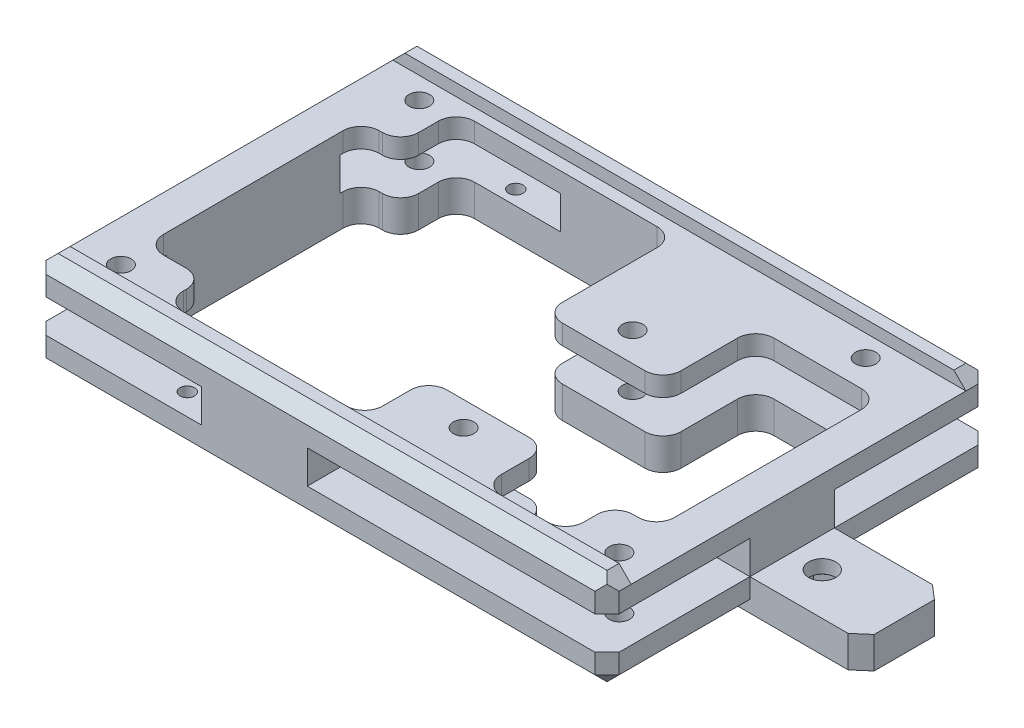
SolidWorks part; units mm, degrees
ref_plane "Front Plane" through (0, 0, 0) normal (0, 0, 1) x (1, 0, 0)
ref_plane "Top Plane" through (0, 0, 0) normal (0, 1, 0) x (1, 0, 0)
ref_plane "Right Plane" through (0, 0, 0) normal (1, 0, 0) x (0, 0, -1)
sketch "Sketch2" plane through (0, 0, 0) normal (0, 1, 0) x (1, 0, 0)
  line L1 (47.5, 31.75) -> (-47.5, 31.75)
  line L2 (47.5, 31.75) -> (47.5, -31.75)
  line L3 (47.5, -31.75) -> (-47.5, -31.75)
  line L4 (-47.5, 31.75) -> (-47.5, -31.75)
  line L5 (47.5, 31.75) -> (-47.5, -31.75) construction
  line L6 (47.5, -31.75) -> (-47.5, 31.75) construction
  point P0 (0, 0)
  dimension "D1" = 95
  dimension "D2" = 63.5
extrude "Boss-Extrude1" add sketch "Sketch2" along normal blind 16
hole_wizard "M3 Clearance Hole1" positions "Sketch7" profile "Sketch8" hole size "M3" standard "ANSI Metric" end condition through all
sketch "Sketch7" plane through (0, 16, 0) normal (0, 1, 0) x (1, 0, 0)
  line L1 (-40.6667, 24.17) -> (34.4633, 24.17)
  line L2 (-40.6667, 24.17) -> (-40.6667, -24.17)
  line L3 (-40.6667, -24.17) -> (34.4633, -24.17)
  line L4 (34.4633, 24.17) -> (34.4633, -24.17)
  line L5 (34.4633, -24.17) -> (41.9633, -24.17) construction
  line L12 (41.9633, -24.17) -> (47.5, -24.17) construction
  line L13 (47.5, -31.75) -> (47.5, 31.75) construction
  line L15 (0, 31.75) -> (0, 24.17) construction
  line L16 (47.5, 31.75) -> (-47.5, 31.75) construction
  line L17 (-3.1017, -24.17) -> (-3.1017, -31.75) construction
  line L18 (-47.5, -31.75) -> (47.5, -31.75) construction
  line L19 (11.1433, -19.17) -> (11.1433, -24.17) construction
  point P33 (-40.6667, -24.17)
  point P34 (34.4633, 24.17)
  point P43 (41.9633, -24.17)
  point P74 (11.1433, -19.17)
  point P80 (11.1433, 8.85)
  point P85 (-3.1017, -24.17)
  point P88 (-39.5367, 24.17)
  dimension "D1" = 48.34
  dimension "D2" = 75.13
  dimension "D3" = 7.5
  dimension "D4" = 51.81
  dimension "D5" = 5
  dimension "D6" = 28.02
  dimension "D7" = 1.13
sketch "Sketch8" plane through (-39.5367, 16, -24.17) normal (1, 0, 0) x (0, 0, 1)
  line L0 (0, 0) -> (0, 16)
  line L1 (0, 16) -> (1.7, 16)
  line L2 (1.7, 16) -> (1.7, 0.025)
  line L3 (1.7, 0.025) -> (1.725, 0)
  line L5 (1.725, 0) -> (0, 0)
  line L6 (-1.7, 0.025) -> (-1.725, 0) construction
  line L11 (0, -6.35) -> (0, 107.95) construction
  dimension "Thru Hole Dia." = 3.4
  dimension "Thru Hole Depth" = 16
  dimension "Near C'Sink Dia." = 3.45
  dimension "Near C'Sink Angle" = 90
sketch "Sketch9" plane through (0, 16, 0) normal (0, 1, 0) x (1, 0, 0)
  line L0 (-34.9742, 19.4874) -> (-34.9742, 22.75)
  line L2 (-37.9742, 16.4874) -> (-38.5, 16.4874)
  line L3 (-41.5, 13.4874) -> (-41.5, -16.2525)
  line L4 (-38.5, -19.2525) -> (-34.7301, -19.2525)
  line L5 (-31.7301, -22.2525) -> (-31.7301, -22.75)
  line L6 (-31.9742, 25.75) -> (-1.6848, 25.75)
  line L7 (-28.7301, -25.75) -> (-1.6848, -25.75)
  line L8 (1.3152, -22.75) -> (1.3152, -18.118)
  line L9 (4.3152, -15.118) -> (17.9713, -15.118)
  line L10 (20.9713, -18.118) -> (20.9713, -22.75)
  line L11 (23.9713, -25.75) -> (31.6479, -25.75)
  line L12 (34.6479, -22.75) -> (34.6479, -20.5605)
  line L13 (37.6479, -17.5605) -> (38.5, -17.5605)
  line L14 (41.5, -14.5605) -> (41.5, 16.4283)
  line L15 (38.5, 19.4283) -> (23.9713, 19.4283)
  line L16 (20.9713, 16.4283) -> (20.9713, 7.055)
  line L17 (17.9713, 4.055) -> (4.3152, 4.055)
  line L18 (1.3152, 7.055) -> (1.3152, 22.75)
  line L19 (-47.5, 31.75) -> (-47.5, -31.75) construction
  line L20 (47.5, 31.75) -> (-47.5, 31.75) construction
  line L21 (47.5, -31.75) -> (47.5, 31.75) construction
  line L22 (-47.5, -31.75) -> (47.5, -31.75) construction
  circle A0 centre (41.9633, -24.17) radius 1.725 construction
  circle A1 centre (34.4633, 24.17) radius 1.725 construction
  circle A2 centre (11.1433, 8.85) radius 1.725 construction
  circle A3 centre (11.1433, -19.17) radius 1.725 construction
  circle A4 centre (-40.6667, -24.17) radius 1.725 construction
  circle A6 centre (41.9633, -24.17) radius 1.725 construction
  circle A7 centre (34.4633, 24.17) radius 1.725 construction
  circle A8 centre (11.1433, 8.85) radius 1.725 construction
  circle A9 centre (11.1433, -19.17) radius 1.725 construction
  circle A10 centre (-40.6667, -24.17) radius 1.725 construction
  arc A12 (-34.9742, 22.75) -> (-31.9742, 25.75) centre (-31.9742, 22.75) cw
  arc A13 (-1.6848, 25.75) -> (1.3152, 22.75) centre (-1.6848, 22.75) cw
  arc A14 (4.3152, 4.055) -> (1.3152, 7.055) centre (4.3152, 7.055) cw
  arc A15 (20.9713, 7.055) -> (17.9713, 4.055) centre (17.9713, 7.055) cw
  arc A16 (23.9713, 19.4283) -> (20.9713, 16.4283) centre (23.9713, 16.4283) ccw
  arc A17 (41.5, 16.4283) -> (38.5, 19.4283) centre (38.5, 16.4283) ccw
  arc A18 (38.5, -17.5605) -> (41.5, -14.5605) centre (38.5, -14.5605) ccw
  arc A19 (34.6479, -20.5605) -> (37.6479, -17.5605) centre (37.6479, -20.5605) cw
  arc A20 (31.6479, -25.75) -> (34.6479, -22.75) centre (31.6479, -22.75) ccw
  arc A21 (20.9713, -22.75) -> (23.9713, -25.75) centre (23.9713, -22.75) ccw
  arc A22 (17.9713, -15.118) -> (20.9713, -18.118) centre (17.9713, -18.118) cw
  arc A23 (1.3152, -18.118) -> (4.3152, -15.118) centre (4.3152, -18.118) cw
  arc A24 (-1.6848, -25.75) -> (1.3152, -22.75) centre (-1.6848, -22.75) ccw
  arc A25 (-31.7301, -22.75) -> (-28.7301, -25.75) centre (-28.7301, -22.75) ccw
  arc A26 (-34.7301, -19.2525) -> (-31.7301, -22.2525) centre (-34.7301, -22.2525) cw
  arc A27 (-41.5, -16.2525) -> (-38.5, -19.2525) centre (-38.5, -16.2525) ccw
  arc A28 (-38.5, 16.4874) -> (-41.5, 13.4874) centre (-38.5, 13.4874) ccw
  arc A29 (-34.9742, 19.4874) -> (-37.9742, 16.4874) centre (-37.9742, 19.4874) cw
  point P37 (11.1433, -15.118)
  point P39 (11.1433, 4.055)
  dimension "D5" = 3
  dimension "D1" = 6
  dimension "D2" = 6
  dimension "D3" = 6
  dimension "D4" = 6
extrude "Cut-Extrude1" cut sketch "Sketch9" against normal up to surface (16 mm away) up to face at (-40.6667, 0, 25.87)
sketch "Sketch10" plane through (0, 0, 0) normal (0, -1, 0) x (1, 0, 0)
  line L1 (-40.6667, 20.9946) -> (-37.9167, 22.5823)
  line L2 (-37.9167, 22.5823) -> (-37.9167, 25.7577)
  line L3 (-37.9167, 25.7577) -> (-40.6667, 27.3454)
  line L4 (-40.6667, 27.3454) -> (-43.4167, 25.7577)
  line L5 (-43.4167, 25.7577) -> (-43.4167, 22.5823)
  line L6 (-43.4167, 22.5823) -> (-40.6667, 20.9946)
  line L7 (-39.5367, -27.3454) -> (-36.7867, -25.7577)
  line L8 (-36.7867, -25.7577) -> (-36.7867, -22.5823)
  line L9 (-36.7867, -22.5823) -> (-39.5367, -20.9946)
  line L10 (-39.5367, -20.9946) -> (-42.2867, -22.5823)
  line L11 (-42.2867, -22.5823) -> (-42.2867, -25.7577)
  line L12 (-42.2867, -25.7577) -> (-39.5367, -27.3454)
  line L13 (8.3933, -10.4377) -> (11.1433, -12.0254)
  line L14 (11.1433, -12.0254) -> (13.8933, -10.4377)
  line L15 (13.8933, -10.4377) -> (13.8933, -7.2623)
  line L16 (13.8933, -7.2623) -> (11.1433, -5.6746)
  line L17 (11.1433, -5.6746) -> (8.3933, -7.2623)
  line L18 (8.3933, -7.2623) -> (8.3933, -10.4377)
  line L19 (8.3933, 17.5823) -> (11.1433, 15.9946)
  line L20 (11.1433, 15.9946) -> (13.8933, 17.5823)
  line L21 (13.8933, 17.5823) -> (13.8933, 20.7577)
  line L22 (13.8933, 20.7577) -> (11.1433, 22.3454)
  line L23 (11.1433, 22.3454) -> (8.3933, 20.7577)
  line L24 (8.3933, 20.7577) -> (8.3933, 17.5823)
  line L31 (41.9633, 20.9946) -> (44.7133, 22.5823)
  line L32 (44.7133, 22.5823) -> (44.7133, 25.7577)
  line L33 (44.7133, 25.7577) -> (41.9633, 27.3454)
  line L34 (41.9633, 27.3454) -> (39.2133, 25.7577)
  line L35 (39.2133, 25.7577) -> (39.2133, 22.5823)
  line L36 (39.2133, 22.5823) -> (41.9633, 20.9946)
  circle A1 centre (41.9633, 24.17) radius 1.7 construction
  circle A2 centre (11.1433, 19.17) radius 1.7 construction
  circle A3 centre (11.1433, -8.85) radius 1.7 construction
  circle A5 centre (-40.6667, 24.17) radius 1.7 construction
  circle A7 centre (41.9633, 24.17) radius 1.7 construction
  circle A8 centre (11.1433, 19.17) radius 1.7 construction
  circle A9 centre (11.1433, -8.85) radius 1.7 construction
  circle A11 centre (-40.6667, 24.17) radius 1.7 construction
  circle A12 centre (-40.6667, 24.17) radius 2.75 construction
  circle A13 centre (-39.5367, -24.17) radius 2.75 construction
  circle A14 centre (11.1433, -8.85) radius 2.75 construction
  circle A15 centre (11.1433, 19.17) radius 2.75 construction
  circle A17 centre (41.9633, 24.17) radius 2.75 construction
  circle A18 centre (-39.5367, -24.17) radius 1.7 construction
  circle A19 centre (-39.5367, -24.17) radius 1.7 construction
  dimension "D1" = 5.5
extrude "Cut-Extrude2" cut sketch "Sketch10" against normal blind 2.4
fillet "Fillet2" radius 2 4 edges at (0, 16, -31.75) (47.5, 16, 0) (0, 16, 31.75) (-47.5, 16, 0) profile chamfer
ref_plane "Plane1" through (0, 8, 0) normal (0, 1, 0) x (1, 0, 0)
sketch "Sketch12" plane through (0, 8, 0) normal (0, 1, 0) x (1, 0, 0)
  line L0 (-31.7301, -22.2525) -> (-31.7301, -22.75) construction
  line L1 (-38.5, -19.2525) -> (-34.7301, -19.2525) construction
  line L2 (-31.7301, -22.2525) -> (-31.7301, -22.75)
  line L3 (-38.5, -19.2525) -> (-34.7301, -19.2525)
  line L14 (-40.6667, -24.17) -> (-40.6213, -18.3738) construction
  line L15 (47.5, -31.75) -> (-47.5, -31.75) construction
  line L16 (-47.5, -31.75) -> (-47.5, 31.75) construction
  line L17 (-19.7301, -31.75) -> (-47.5, -31.75)
  line L18 (-47.5, -31.75) -> (-47.5, -15.7525)
  line L23 (-19.7301, -31.75) -> (-19.7301, -25.75)
  line L24 (-28.7301, -25.75) -> (-1.6848, -25.75) construction
  line L25 (-19.7301, -25.75) -> (-28.7301, -25.75)
  line L26 (-47.5, -15.7525) -> (-41.5, -15.7525)
  line L27 (-41.5, 13.4874) -> (-41.5, -16.2525) construction
  line L28 (-41.5, -15.7525) -> (-41.5, -16.2525)
  arc A0 (-31.7301, -22.75) -> (-28.7301, -25.75) centre (-28.7301, -22.75) ccw construction
  arc A1 (-31.7301, -22.2525) -> (-34.7301, -19.2525) centre (-34.7301, -22.2525) ccw construction
  arc A2 (-41.5, -16.2525) -> (-38.5, -19.2525) centre (-38.5, -16.2525) ccw construction
  arc A3 (-31.7301, -22.75) -> (-28.7301, -25.75) centre (-28.7301, -22.75) ccw
  arc A4 (-31.7301, -22.2525) -> (-34.7301, -19.2525) centre (-34.7301, -22.2525) ccw
  arc A5 (-41.5, -16.2525) -> (-38.5, -19.2525) centre (-38.5, -16.2525) ccw
  circle A6 centre (-40.6667, -24.17) radius 1.7 construction
  circle A7 centre (-40.6667, -24.17) radius 1.7
  dimension "D1" = 9
  dimension "D2" = 0.5
extrude "Cut-Extrude3" cut sketch "Sketch12" along normal blind 2.75 and the other way blind 2.75
sketch "Sketch14" plane through (0, 8, 0) normal (0, 1, 0) x (1, 0, 0)
  line L0 (-34.9742, 22.75) -> (-34.9742, 19.4874) construction
  line L1 (-34.9742, 22.75) -> (-34.9742, 19.4874)
  line L3 (-47.5, -31.75) -> (-47.5, 31.75) construction
  line L4 (-47.5, 12.9874) -> (-47.5, 31.75)
  line L5 (-31.9742, 25.75) -> (-31.9742, 31.75) construction
  line L6 (-47.5, 31.75) -> (47.5, 31.75) construction
  line L8 (-47.5, 31.75) -> (-11.9742, 31.75)
  line L9 (-37.9742, 16.4874) -> (-38.5, 16.4874) construction
  line L10 (-37.9742, 16.4874) -> (-38.5, 16.4874)
  line L11 (-31.9742, 25.75) -> (-11.9742, 25.75)
  line L12 (-1.6848, 25.75) -> (-31.9742, 25.75) construction
  line L13 (-11.9742, 25.75) -> (-11.9742, 31.75)
  line L16 (-47.5, 12.9874) -> (-41.5, 12.9874)
  line L17 (-41.5, 13.4874) -> (-41.5, -16.2525) construction
  line L18 (-41.5, 12.9874) -> (-41.5, 13.4874)
  arc A1 (-38.5, 16.4874) -> (-41.5, 13.4874) centre (-38.5, 13.4874) ccw construction
  arc A2 (-37.9742, 16.4874) -> (-34.9742, 19.4874) centre (-37.9742, 19.4874) ccw construction
  arc A3 (-31.9742, 25.75) -> (-34.9742, 22.75) centre (-31.9742, 22.75) ccw construction
  arc A5 (-38.5, 16.4874) -> (-41.5, 13.4874) centre (-38.5, 13.4874) ccw
  arc A6 (-37.9742, 16.4874) -> (-34.9742, 19.4874) centre (-37.9742, 19.4874) ccw
  arc A7 (-31.9742, 25.75) -> (-34.9742, 22.75) centre (-31.9742, 22.75) ccw
  dimension "D1" = 20
  dimension "D2" = 0.5
extrude "Cut-Extrude10" cut sketch "Sketch14" against normal blind 2.75 and the other way blind 2.75
sketch "Sketch13" plane through (0, 8, 0) normal (0, 1, 0) x (1, 0, 0)
  line L1 (20.9713, -18.118) -> (20.9713, -22.75) construction
  line L2 (4.3152, -15.118) -> (17.9713, -15.118) construction
  line L3 (1.3152, -22.75) -> (1.3152, -18.118) construction
  line L4 (47.5, 31.75) -> (47.5, -31.75) construction
  line L5 (20.9713, -18.118) -> (20.9713, -22.75)
  line L6 (4.3152, -15.118) -> (17.9713, -15.118)
  line L7 (1.3152, -22.75) -> (1.3152, -18.118)
  line L9 (37.6479, -17.5605) -> (38.5, -17.5605) construction
  line L10 (34.6479, -22.75) -> (34.6479, -20.5605) construction
  line L12 (23.9713, -25.75) -> (31.6479, -25.75) construction
  line L13 (-2.1848, -31.75) -> (47.5, -31.75)
  line L14 (47.5, -31.75) -> (-47.5, -31.75) construction
  line L15 (47.5, -8.0605) -> (47.5, -31.75)
  line L16 (37.6479, -17.5605) -> (38.5, -17.5605)
  line L18 (34.6479, -22.75) -> (34.6479, -20.5605)
  line L20 (23.9713, -25.75) -> (31.6479, -25.75)
  line L22 (41.5, -14.5605) -> (41.5, -8.0605)
  line L23 (41.5, -14.5605) -> (41.5, 16.4283) construction
  line L24 (41.5, -8.0605) -> (47.5, -8.0605)
  line L25 (-2.1848, -31.75) -> (-2.1848, -25.75)
  line L26 (-28.7301, -25.75) -> (-1.6848, -25.75) construction
  line L27 (-2.1848, -25.75) -> (-1.6848, -25.75)
  arc A0 (-1.6848, -25.75) -> (1.3152, -22.75) centre (-1.6848, -22.75) ccw construction
  arc A1 (20.9713, -22.75) -> (23.9713, -25.75) centre (23.9713, -22.75) ccw construction
  arc A2 (20.9713, -18.118) -> (17.9713, -15.118) centre (17.9713, -18.118) ccw construction
  arc A3 (4.3152, -15.118) -> (1.3152, -18.118) centre (4.3152, -18.118) ccw construction
  arc A4 (-1.6848, -25.75) -> (1.3152, -22.75) centre (-1.6848, -22.75) ccw
  arc A5 (20.9713, -22.75) -> (23.9713, -25.75) centre (23.9713, -22.75) ccw
  arc A6 (20.9713, -18.118) -> (17.9713, -15.118) centre (17.9713, -18.118) ccw
  arc A7 (4.3152, -15.118) -> (1.3152, -18.118) centre (4.3152, -18.118) ccw
  arc A15 (38.5, -17.5605) -> (41.5, -14.5605) centre (38.5, -14.5605) ccw construction
  arc A16 (37.6479, -17.5605) -> (34.6479, -20.5605) centre (37.6479, -20.5605) ccw construction
  arc A17 (31.6479, -25.75) -> (34.6479, -22.75) centre (31.6479, -22.75) ccw construction
  arc A18 (38.5, -17.5605) -> (41.5, -14.5605) centre (38.5, -14.5605) ccw
  arc A19 (37.6479, -17.5605) -> (34.6479, -20.5605) centre (37.6479, -20.5605) ccw
  arc A20 (31.6479, -25.75) -> (34.6479, -22.75) centre (31.6479, -22.75) ccw
  dimension "D1" = 6.5
  dimension "D2" = 0.5
extrude "Cut-Extrude11" cut sketch "Sketch13" against normal blind 2.75 and the other way blind 2.75
sketch "Sketch15" plane through (0, 8, 0) normal (0, 1, 0) x (1, 0, 0)
  line L0 (38.5, 19.4283) -> (23.9713, 19.4283) construction
  line L1 (20.9713, 16.4283) -> (20.9713, 7.055) construction
  line L2 (17.9713, 4.055) -> (4.3152, 4.055) construction
  line L3 (1.3152, 7.055) -> (1.3152, 22.75) construction
  line L4 (38.5, 19.4283) -> (23.9713, 19.4283)
  line L5 (20.9713, 16.4283) -> (20.9713, 7.055)
  line L6 (17.9713, 4.055) -> (4.3152, 4.055)
  line L7 (1.3152, 7.055) -> (1.3152, 22.75)
  line L8 (-1.6848, 25.75) -> (-12.6848, 25.75)
  line L10 (-1.6848, 25.75) -> (-31.9742, 25.75) construction
  line L11 (-12.6848, 25.75) -> (-12.6848, 31.75)
  line L12 (-47.5, 31.75) -> (47.5, 31.75) construction
  line L13 (-12.6848, 31.75) -> (47.5, 31.75)
  line L14 (47.5, 31.75) -> (47.5, 5.9283)
  line L15 (47.5, 31.75) -> (47.5, -31.75) construction
  line L16 (47.5, 5.9283) -> (41.5, 5.9283)
  line L17 (41.5, -14.5605) -> (41.5, 16.4283) construction
  line L18 (41.5, 5.9283) -> (41.5, 16.4283)
  line L19 (11.1433, 8.85) -> (11.1433, 4.055) construction
  line L20 (31.2357, 19.4283) -> (31.2357, 24.17) construction
  line L21 (31.2357, 24.17) -> (34.4633, 24.17) construction
  line L22 (-39.5367, 24.17) -> (-39.5367, 8.85) construction
  line L23 (-39.5367, 8.85) -> (11.1433, 8.85) construction
  circle A0 centre (34.4633, 24.17) radius 1.725 construction
  circle A1 centre (11.1433, 8.85) radius 1.725 construction
  arc A2 (41.5, 16.4283) -> (38.5, 19.4283) centre (38.5, 16.4283) ccw construction
  arc A3 (23.9713, 19.4283) -> (20.9713, 16.4283) centre (23.9713, 16.4283) ccw construction
  arc A4 (17.9713, 4.055) -> (20.9713, 7.055) centre (17.9713, 7.055) ccw construction
  arc A5 (1.3152, 7.055) -> (4.3152, 4.055) centre (4.3152, 7.055) ccw construction
  arc A6 (1.3152, 22.75) -> (-1.6848, 25.75) centre (-1.6848, 22.75) ccw construction
  circle A7 centre (34.4633, 24.17) radius 1.725 construction
  circle A8 centre (11.1433, 8.85) radius 1.725 construction
  arc A9 (41.5, 16.4283) -> (38.5, 19.4283) centre (38.5, 16.4283) ccw
  arc A10 (23.9713, 19.4283) -> (20.9713, 16.4283) centre (23.9713, 16.4283) ccw
  arc A11 (17.9713, 4.055) -> (20.9713, 7.055) centre (17.9713, 7.055) ccw
  arc A12 (1.3152, 7.055) -> (4.3152, 4.055) centre (4.3152, 7.055) ccw
  arc A13 (1.3152, 22.75) -> (-1.6848, 25.75) centre (-1.6848, 22.75) ccw
  circle A16 centre (-40.6667, -24.17) radius 1.7 construction
  circle A17 centre (-40.6667, -24.17) radius 1.7
  circle A18 centre (-39.5367, 24.17) radius 1.725 construction
  circle A19 centre (-39.5367, 24.17) radius 1.725 construction
  dimension "D1" = 11
  dimension "D2" = 10.5
extrude "Cut-Extrude12" cut sketch "Sketch15" against normal blind 2.75 and the other way blind 2.75
chamfer "Chamfer1" distance 2 angle 45 8 edges at (47.5, 0, 0) (47.5, 2.625, -31.75) (47.5, 2.625, 31.75) (0, 0, 31.75) (-47.5, 2.625, 31.75) (-47.5, 0, 0) (0, 0, -31.75) (-47.5, 2.625, -31.75)
chamfer "Chamfer2" distance 2 angle 45 4 edges at (-47.5, 12.375, 31.75) (47.5, 12.375, 31.75) (47.5, 12.375, -31.75) (-47.5, 12.375, -31.75)
sketch "Sketch18" plane through (0, 0, -31.75) normal (0, 0, -1) x (-1, 0, 0)
  line L4 (17.7301, 10.75) -> (0.1848, 10.75)
  line L5 (-45.5, 10.75) -> (45.5, 10.75) construction
  line L6 (0.1848, 10.75) -> (0.1848, 5.25)
  line L7 (-45.5, 5.25) -> (45.5, 5.25) construction
  line L8 (0.1848, 5.25) -> (17.7301, 5.25)
  line L9 (17.7301, 5.25) -> (17.7301, 10.75)
  line L10 (0.1848, 8) -> (2.1848, 8) construction
  line L11 (2.1848, 10.75) -> (2.1848, 5.25) construction
  line L12 (17.7301, 8) -> (19.7301, 8) construction
  line L13 (19.7301, 5.25) -> (19.7301, 10.75) construction
  dimension "D1" = 2
extrude "Boss-Extrude2" add sketch "Sketch18" against normal up to surface (6 mm away) up to face at (-16.8295, 2.625, -25.75)
ref_plane "Plane2" through (0, 0, 1.0661) normal (0, 0, 1) x (1, 0, 0)
sketch "Sketch40" plane through (0, 16, 0) normal (0, 1, 0) x (1, 0, 0)
  line L0 (-62.155, 27.75) -> (62.155, 27.75)
  line L1 (-62.155, -27.75) -> (62.155, -27.75)
  line L2 (62.155, -27.75) -> (62.155, 27.75)
  line L3 (-62.155, 27.75) -> (-62.155, -27.75)
  line L4 (0, -27.75) -> (0, -29.75) construction
  line L5 (-45.5, -29.75) -> (45.5, -29.75) construction
  line L6 (0, 27.75) -> (0, 29.75) construction
  line L7 (45.5, 29.75) -> (-45.5, 29.75) construction
  dimension "D1" = 2
extrude "Cut-Extrude16" cut sketch "Sketch40" against normal blind 2
sketch "Sketch43" plane through (0, 0, 8.0605) normal (0, 0, 1) x (1, 0, 0)
  line L0 (45.5, 2) -> (45.5, 0) construction
  line L1 (45.5, 2) -> (45.5, 0)
  line L2 (45.5, 0) -> (57.5, 0)
  line L3 (57.5, 0) -> (60.0844, 5.25)
  line L4 (60.0844, 5.25) -> (47.5, 5.25)
  line L5 (47.5, 5.25) -> (47.5, 2)
  line L6 (47.5, 2) -> (45.5, 2)
  dimension "D1" = 10
extrude "Boss-Extrude3" add sketch "Sketch43" against normal up to surface (13.9888 mm away) up to face at (44.5, 8, -5.9283)
sketch "Sketch48" plane through (0, 0, 0) normal (0, -1, 0) x (1, 0, 0)
  line L0 (47.5, 8.0605) -> (47.5, -5.9283) construction
  line L2 (47.5, 8.0605) -> (57.5, 8.0605) construction
  line L3 (52.5, -2.8887) -> (55.925, -0.9113)
  line L4 (55.925, -0.9113) -> (55.925, 3.0435)
  line L5 (55.925, 3.0435) -> (52.5, 5.021)
  line L6 (52.5, 5.021) -> (49.075, 3.0435)
  line L7 (49.075, 3.0435) -> (49.075, -0.9113)
  line L8 (49.075, -0.9113) -> (52.5, -2.8887)
  circle A0 centre (52.5, 1.0661) radius 3.425 construction
  point P4 (52.5, 8.0605)
  point P16 (47.5, 1.0661)
  dimension "D1" = 6.85
extrude "Cut-Extrude18" cut sketch "Sketch48" against normal blind 3
hole_wizard "M4 Clearance Hole1" positions "Sketch49" profile "Sketch50" hole size "M4" standard "ANSI Metric" end condition through all
sketch "Sketch49" plane through (0, 3, 0) normal (0, -1, 0) x (-1, 0, 0)
  line L0 (-49.075, -3.0435) -> (-49.075, 0.9113) construction
  line L1 (-55.925, 0.9113) -> (-55.925, -3.0435) construction
  line L2 (-49.075, -3.0435) -> (-49.075, 0.9113)
  line L3 (-55.925, 0.9113) -> (-55.925, -3.0435)
  point P5 (-52.5, -1.0661)
  point P10 (-55.925, -1.0661)
sketch "Sketch50" plane through (52.5, 3, 1.0661) normal (1, 0, 0) x (0, 0, -1)
  line L0 (0, 0) -> (0, 13)
  line L1 (0, 13) -> (2.25, 13)
  line L2 (2.25, 13) -> (2.25, 0.025)
  line L3 (2.25, 0.025) -> (2.275, 0)
  line L5 (2.275, 0) -> (0, 0)
  line L6 (-2.25, 0.025) -> (-2.275, 0) construction
  line L11 (0, -6.35) -> (0, 107.95) construction
  dimension "Thru Hole Dia." = 4.5
  dimension "Thru Hole Depth" = 13
  dimension "Near C'Sink Dia." = 4.55
  dimension "Near C'Sink Angle" = 90
sketch "Sketch52" plane through (0, 5.25, 0) normal (0, 1, 0) x (1, 0, 0)
  line L0 (60.0844, 5.9283) -> (63.7744, 5.9283)
  line L1 (63.7744, 5.9283) -> (66.0909, 3.9289)
  line L2 (66.0909, 3.9289) -> (66.0909, -6.0611)
  line L3 (66.0909, -6.0611) -> (63.7744, -8.0605)
  line L4 (63.7744, -8.0605) -> (60.0844, -8.0605)
  line L5 (60.0844, 5.9283) -> (60.0844, -8.0605) construction
  line L6 (60.0844, 5.9283) -> (60.0844, -8.0605)
  point P10 (60.0844, -1.0661)
  point P11 (66.0909, -1.0661)
  dimension "D1" = 3.69
  dimension "D2" = 3.06
  dimension "D3" = 9.99
extrude "Boss-Extrude4" add sketch "Sketch52" against normal up to surface (5.25 mm away) separate body up to face at (52.5, 0, 1.0661)
sketch "Sketch53" plane through (0, 0, 8.0605) normal (0, 0, 1) x (1, 0, 0)
  line L0 (60.0844, 0) -> (60.0844, 5.25) construction
  line L1 (57.5, 0) -> (60.0844, 5.25) construction
  line L2 (60.0844, 0) -> (60.0844, 5.25)
  line L3 (57.5, 0) -> (60.0844, 5.25)
  line L4 (57.5, 0) -> (60.0844, 0)
extrude "Boss-Extrude5" add sketch "Sketch53" against normal up to surface (13.9888 mm away) up to face at (61.9294, 2.625, -5.9283)
hole_wizard "M2 Clearance Hole1" positions "Sketch56" profile "Sketch57" hole size "M2" standard "ANSI Metric"
sketch "Sketch56" plane through (0, 0, 0) normal (0, -1, 0) x (-1, 0, 0)
  line L0 (27.5367, 28.17) -> (27.5367, 31.75) construction
  line L1 (-45.5, 31.75) -> (45.5, 31.75) construction
  line L2 (27.5367, 28.17) -> (27.5367, 25.75) construction
  line L3 (1.6848, 25.75) -> (31.9742, 25.75) construction
  line L4 (27.5367, 28.17) -> (39.5367, 28.17) construction
  line L5 (39.5367, 28.17) -> (39.5367, 24.17) construction
  line L6 (25.6667, -28.17) -> (40.6667, -28.17) construction
  line L7 (40.6667, -28.17) -> (40.6667, -24.17) construction
  point P0 (27.5367, 28.17)
  point P22 (25.6667, -28.17)
  dimension "D1" = 12
  dimension "D2" = 4
  dimension "D3" = 4
  dimension "D4" = 15
sketch "Sketch57" plane through (-27.5367, 0, -28.17) normal (1, 0, 0) x (0, 0, -1)
  line L0 (0, 0) -> (0, 5.971)
  line L1 (0, 5.971) -> (1.2, 5.25)
  line L2 (1.2, 5.25) -> (1.2, 0.025)
  line L3 (1.2, 0.025) -> (1.225, 0)
  line L5 (1.225, 0) -> (0, 0)
  line L6 (-1.2, 0.025) -> (-1.225, 0) construction
  line L10 (0, 5.971) -> (-1.2, 5.25) construction
  line L11 (0, -6.35) -> (0, 107.95) construction
  dimension "Hole Dia." = 2.4
  dimension "Hole Depth" = 5.25
  dimension "Near C'Sink Dia." = 2.45
  dimension "Near C'Sink Angle" = 90
  dimension "Drill Angle" = 118
sketch "Sketch59" plane through (-47.5, 0, 0) normal (-1, 0, 0) x (0, 0, 1)
  line L0 (-13.25, 2.4817) -> (-13.25, 4.535)
  line L1 (-13.25, 4.535) -> (13.25, 4.535)
  line L2 (13.25, 4.535) -> (13.25, 2.4817)
  line L3 (13.25, 2.4817) -> (-13.25, 2.4817)
  point P2 (0, 4.535)
  dimension "D1" = 26.5
extrude "Boss-Extrude6" [suppressed] add sketch "Sketch59" along normal blind 46
sketch "Sketch60" [suppressed] plane through (0, 2.4817, 0) normal (0, -1, 0) x (1, 0, 0)
  line L0 (-47.5, 15.25) -> (-95.5, 15.25)
  line L1 (-95.5, 15.25) -> (-95.5, -15.25)
  line L2 (-95.5, -15.25) -> (-47.5, -15.25)
  line L3 (-47.5, 13.25) -> (-47.5, 15.25)
  line L4 (-47.5, -13.25) -> (-47.5, 13.25)
  line L5 (-47.5, 13.25) -> (-93.5, 13.25)
  line L6 (-93.5, 13.25) -> (-93.5, -13.25)
  line L7 (-93.5, -13.25) -> (-47.5, -13.25)
  line L9 (-47.5, 13.25) -> (-93.5, 13.25)
  line L10 (-93.5, 13.25) -> (-93.5, -13.25)
  line L11 (-93.5, -13.25) -> (-47.5, -13.25)
  line L12 (-47.5, -15.25) -> (-47.5, -13.25)
  dimension "D1" = 0
  dimension "D2" = 2
extrude "Boss-Extrude7" [suppressed] add sketch "Sketch60" against normal blind 8
